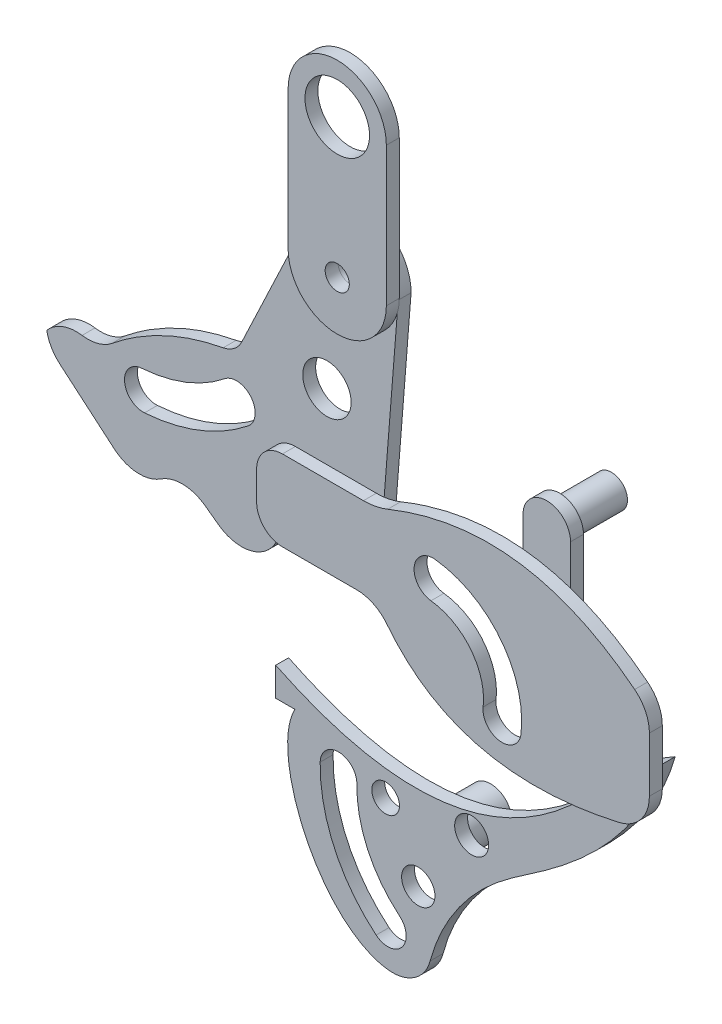
SolidWorks part; units mm, degrees
ref_plane "Front Plane" through (0, 0, 0) normal (0, 0, 1) x (1, 0, 0)
ref_plane "Top Plane" through (0, 0, 0) normal (0, 1, 0) x (1, 0, 0)
ref_plane "Right Plane" through (0, 0, 0) normal (1, 0, 0) x (0, 0, -1)
sketch "Sketch2" plane through (0, 0, 0) normal (0, 0, 1) x (1, 0, 0)
  line L0 (103.898, 229.4662) -> (99.9654, 179.6542)
  line L1 (99.9654, 179.6542) -> (80.7398, 179.6542)
  line L2 (80.7398, 179.6542) -> (79.6265, 165.5529)
  line L3 (79.6265, 165.5529) -> (60.2033, 179.6542)
  line L4 (83.7984, 229.4662) -> (60.2033, 179.6542)
  arc A0 (103.7735, 227.8892) -> (83.7984, 229.4662) centre (93.8482, 229.4662) ccw
extrude "Boss-Extrude1" add sketch "Sketch2" against normal blind 2.54 contours L0 A0 L4 L3 L2 L1 region at (85.8639, 202.4845, 0)
sketch "Sketch3" plane through (0, 0, 0) normal (0, 0, 1) x (1, 0, 0)
  line L0 (155.829, 186.5321) -> (155.829, 166.3376)
  line L1 (78.6053, 194.4484) -> (102.1925, 194.4484)
  line L2 (78.6053, 194.4484) -> (78.6053, 178.6159)
  line L3 (78.6053, 178.6159) -> (102.1925, 178.6159)
  spline S0 degree 2 poles (102.1925, 194.4484) (132.0004, 207.7356) (155.829, 186.5321) knots 0 0 0 1 1 1
  spline S1 degree 2 poles (102.1925, 178.6159) (117.1359, 155.191) (155.829, 166.3376) knots 0 0 0 1 1 1
extrude "Boss-Extrude2" add sketch "Sketch3" along normal blind 2.54
sketch "Sketch4" plane through (0, 0, 0) normal (0, 0, 1) x (1, 0, 0)
  line L0 (155.829, 166.3376) -> (155.829, 186.5321) construction
  line L1 (83.5737, 149.6445) -> (79.8215, 149.6445)
  line L2 (79.8215, 149.6445) -> (79.8215, 155.2728)
  line L3 (147.8301, 171.6887) -> (155.829, 176.4349)
  circle A0 centre (109.3701, 139.3259) radius 3.7522
  arc A1 (92.1657, 143.0781) -> (101.8656, 121.972) centre (119.0233, 142.6393) ccw construction
  arc A2 (88.5589, 143.137) -> (99.5615, 119.1965) centre (119.0233, 142.6393) ccw
  arc A3 (95.7725, 143.0192) -> (104.1698, 124.7474) centre (119.0233, 142.6393) ccw
  arc A4 (95.7725, 143.0192) -> (88.5589, 143.137) centre (92.1657, 143.0781) ccw
  arc A5 (99.5615, 119.1965) -> (104.1698, 124.7474) centre (101.8656, 121.972) ccw
  spline S0 degree 2 poles (147.8301, 171.6887) (121.1355, 135.1528) (79.8215, 155.2728) knots 0 0 0 1 1 1
  spline S1 degree 3 poles (155.829, 176.4349) (152.2465, 163.8385) (140.1424, 151.0301) (117.9718, 137.2974) (110.5156, 124.9991) (109.3701, 115.8746) knots 0 0 0 0 0.486939 0.650238 1 1 1 1
  spline S2 degree 3 poles (109.3701, 115.8746) (92.5937, 107.2545) (77.4038, 137.936) (83.5737, 149.6445) knots 0 0 0 0 1 1 1 1
  point P20 (94.6163, 131.4223)
extrude "Boss-Extrude3" add sketch "Sketch4" against normal blind 2.54
sketch "Sketch5" plane through (0, 0, 0) normal (0, 0, 1) x (1, 0, 0)
  line L1 (128.4438, 185.7997) -> (137.7867, 185.7997)
  line L2 (128.4438, 185.7997) -> (128.4438, 205.2642)
  line L3 (128.4438, 205.2642) -> (137.7867, 205.2642)
  line L4 (137.7867, 185.7997) -> (137.7867, 205.2642)
extrude "Boss-Extrude4" add sketch "Sketch5" against normal blind 2.54
sketch "Sketch6" plane through (0, 0, 0) normal (0, 0, 1) x (1, 0, 0)
  line L0 (137.7867, 205.2642) -> (128.4438, 205.2642) construction
  circle A0 centre (133.1152, 205.2642) radius 4.6715
extrude "Boss-Extrude5" add sketch "Sketch6" against normal blind 2.54
sketch "Sketch7" plane through (0, 0, 0) normal (0, 0, 1) x (1, 0, 0)
  circle A0 centre (133.1152, 205.2642) radius 1.3253
extrude "Cut-Extrude1" cut sketch "Sketch7" against normal blind 2.54
sketch "Sketch8" plane through (0, 0, 0) normal (0, 0, 1) x (1, 0, 0)
  line L0 (83.7984, 229.4662) -> (60.2033, 179.6542) construction
  line L1 (53.4307, 171.6832) -> (33.6806, 188.4637)
  line L2 (33.6806, 188.4637) -> (38.6126, 194.2685)
  line L3 (38.6126, 194.2685) -> (44.6513, 191.3702)
  line L4 (72.0008, 204.5602) -> (60.2033, 179.6542)
  spline S0 degree 2 poles (72.0008, 204.5602) (56.4395, 202.4235) (44.6513, 191.3702) knots 0 0 0 1 1 1
  spline S1 degree 2 poles (60.2033, 179.6542) (56.817, 175.6687) (53.4307, 171.6832) knots 0 0 0 1 1 1
extrude "Boss-Extrude6" add sketch "Sketch8" against normal blind 2.54
sketch "Sketch9" plane through (0, 0, 0) normal (0, 0, 1) x (1, 0, 0)
  circle A0 centre (94.4559, 229.8811) radius 2.4136
extrude "Cut-Extrude2" cut sketch "Sketch9" against normal blind 2.54
sketch "Sketch11" plane through (0, 0, 0) normal (0, 0, 1) x (1, 0, 0)
  line L0 (94.4559, 229.8811) -> (94.4559, 257.2304) construction
  line L1 (84.8014, 229.8811) -> (84.8014, 257.2304)
  line L2 (104.1105, 229.8811) -> (104.1105, 257.2304)
  arc A0 (84.8014, 229.8811) -> (104.1105, 229.8811) centre (94.4559, 229.8811) ccw
  arc A1 (104.1105, 257.2304) -> (84.8014, 257.2304) centre (94.4559, 257.2304) ccw
  point P3 (94.4559, 243.5558)
extrude "Boss-Extrude7" add sketch "Sketch11" along normal blind 2.54
sketch "Sketch12" plane through (0, 0, 2.54) normal (0, 0, 1) x (1, 0, 0)
  circle A0 centre (94.4559, 257.2304) radius 6.35
  dimension "D1" = 12.7
extrude "Cut-Extrude3" cut sketch "Sketch12" against normal blind 2.54
sketch "Sketch13" plane through (0, 0, 2.54) normal (0, 0, 1) x (1, 0, 0)
  circle A0 centre (94.4559, 229.8811) radius 2.3733
extrude "Cut-Extrude4" cut sketch "Sketch13" against normal blind 2.54
sketch "Sketch14" plane through (0, 0, 0) normal (0, 0, 1) x (1, 0, 0)
  circle A0 centre (133.1152, 205.2642) radius 3.1683
extrude "Boss-Extrude8" add sketch "Sketch14" against normal blind 12.7
sketch "Sketch15" plane through (0, 0, 0) normal (0, 0, 1) x (1, 0, 0)
  circle A0 centre (109.3701, 139.3259) radius 4.1855
extrude "Boss-Extrude9" add sketch "Sketch15" against normal blind 12.7
fillet "Fillet1" radius 5.08 2 edges at (78.6053, 178.6159, 1.27) (78.6053, 194.4484, 1.27)
fillet "Fillet2" radius 5.08 1 edges at (72.0008, 204.5602, -1.27)
fillet "Fillet3" radius 7.62 2 edges at (60.2033, 179.6542, -1.27) (79.6265, 165.5529, -1.27)
fillet "Fillet4" radius 7.62 1 edges at (102.1925, 178.6159, 1.27)
fillet "Fillet5" radius 12.7 1 edges at (102.1925, 194.4484, 1.27)
fillet "Fillet6" radius 7.62 2 edges at (155.829, 166.3376, 1.27) (155.829, 186.5321, 1.27)
fillet "Fillet7" radius 7.62 1 edges at (38.6126, 194.2685, -1.27)
fillet "Fillet8" radius 7.62 2 edges at (33.6806, 188.4637, -1.27) (53.4307, 171.6832, -1.27)
fillet "Fillet9" radius 7.62 1 edges at (44.6513, 191.3702, -1.27)
fillet "Fillet10" radius 7.62 1 edges at (109.3701, 115.8746, -1.27)
sketch "Sketch16" plane through (0, 0, 2.54) normal (0, 0, 1) x (1, 0, 0)
  arc A0 (53.763, 189.003) -> (72.1061, 196.1808) centre (51.4843, 221.8535) ccw construction
  arc A1 (54.0172, 185.3383) -> (74.4066, 193.3168) centre (51.4843, 221.8535) ccw
  arc A2 (53.5088, 192.6678) -> (69.8055, 199.0448) centre (51.4843, 221.8535) ccw
  arc A3 (53.5088, 192.6678) -> (54.0172, 185.3383) centre (53.763, 189.003) ccw
  arc A4 (74.4066, 193.3168) -> (69.8055, 199.0448) centre (72.1061, 196.1808) ccw
  arc A5 (113.3115, 187.7673) -> (126.8695, 170.66) centre (111.5368, 172.4347) cw construction
  arc A6 (130.5938, 170.2289) -> (113.7426, 191.4916) centre (111.5368, 172.4347) ccw
  arc A7 (123.1452, 171.091) -> (112.8805, 184.043) centre (111.5368, 172.4347) ccw
  arc A8 (123.1452, 171.091) -> (130.5938, 170.2289) centre (126.8695, 170.66) ccw
  arc A9 (113.7426, 191.4916) -> (112.8805, 184.043) centre (113.3115, 187.7673) ccw
  point P3 (63.4838, 191.1882)
  point P8 (123.6336, 182.0216)
extrude "Cut-Extrude5" cut sketch "Sketch16" against normal blind 116.84
sketch "Sketch17" plane through (0, 0, 0) normal (0, 0, 1) x (1, 0, 0)
  circle A0 centre (89.891, 207.4119) radius 4.7578
  circle A1 centre (143.4748, 182.5099) radius 3.9759
extrude "Cut-Extrude6" cut sketch "Sketch17" against normal blind 116.84
sketch "Sketch18" plane through (0, 0, 0) normal (0, 0, 1) x (1, 0, 0)
  circle A0 centre (118.3433, 145.5738) radius 3.3405
  circle A1 centre (107.8466, 131.6251) radius 3.2759
  circle A2 centre (101.4295, 143.4809) radius 2.7191
extrude "Cut-Extrude7" cut sketch "Sketch18" against normal blind 2.54
